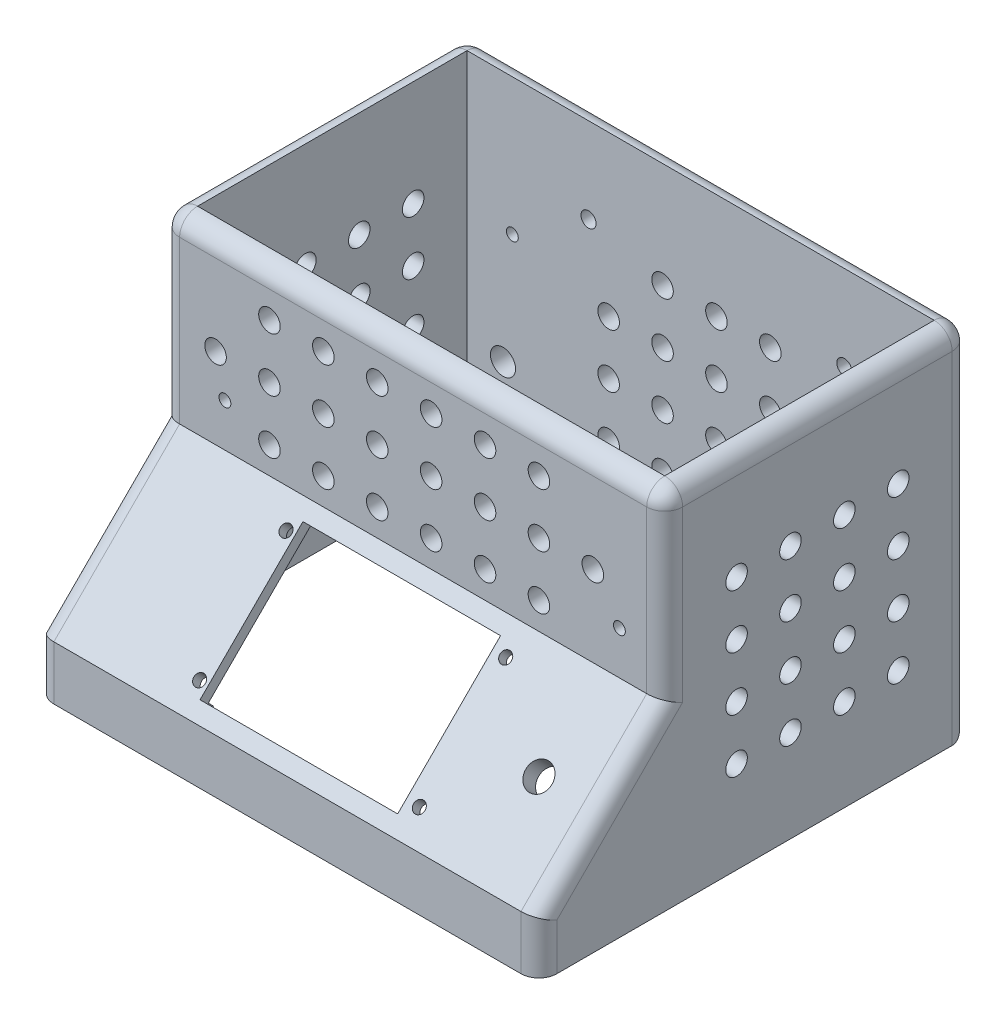
SolidWorks part; units mm, degrees
ref_plane "Alzado" through (0, 0, 0) normal (0, 0, 1) x (1, 0, 0)
ref_plane "Planta" through (0, 0, 0) normal (0, 1, 0) x (1, 0, 0)
ref_plane "Vista lateral" through (0, 0, 0) normal (1, 0, 0) x (0, 0, -1)
sketch "Sketch2" plane through (0, 0, 0) normal (1, 0, 0) x (0, 0, -1)
  line L0 (-77.5, -50) -> (-77.5, -35)
  line L1 (-42.5, 50) -> (42.5, 50)
  line L2 (-42.5, 50) -> (-42.5, -50)
  line L3 (-42.5, -50) -> (42.5, -50)
  line L4 (42.5, 50) -> (42.5, -50)
  line L5 (-42.5, 50) -> (42.5, -50) construction
  line L6 (-42.5, -50) -> (42.5, 50) construction
  line L7 (-77.5, -50) -> (-42.5, -50)
  line L8 (-77.5, -35) -> (-42.5, 0)
  line L9 (-77.5, -35) -> (-42.5, -35) construction
  point P0 (0, 0)
  dimension "D1" = 45
  dimension "D2" = 85
  dimension "D3" = 35
  dimension "D4" = 100
  dimension "D5" = 15
extrude "Boss-Extrude1" add sketch "Sketch2" along normal mid plane 140
shell "Shell1" thickness 5
sketch "Sketch3" plane through (0, -50, 0) normal (0, -1, 0) x (1, 0, 0)
  line L1 (-65, 72.5) -> (65, 72.5)
  line L2 (-65, 72.5) -> (-65, -37.5)
  line L3 (-65, -37.5) -> (65, -37.5)
  line L4 (-70, 77.5) -> (-70, -42.5)
  line L5 (-70, -42.5) -> (70, -42.5)
  line L6 (70, -42.5) -> (70, 77.5)
  line L7 (70, 77.5) -> (-70, 77.5)
  line L8 (-70, 77.5) -> (-70, -42.5)
  line L9 (-70, -42.5) -> (70, -42.5)
  line L10 (70, -42.5) -> (70, 77.5)
  line L11 (70, 77.5) -> (-70, 77.5)
  line L12 (65, 72.5) -> (65, -37.5)
  line L13 (-65, 72.5) -> (65, -37.5) construction
  line L14 (-65, -37.5) -> (65, 72.5) construction
  point P2 (0, 17.5)
  dimension "D2" = 5
  dimension "D3" = 5
  dimension "D4" = 5
  dimension "D5" = 5
  dimension "D1" = 0
extrude "Cut-Extrude1" cut sketch "Sketch3" against normal up to surface (5 mm away) contours L2 L1 L12 L3
sketch "Sketch4" plane through (0, 21.25, 21.25) normal (0, 0.7071, 0.7071) x (1, 0, 0)
  line L0 (70, -79.5495) -> (-70, -30.052) construction
  line L1 (-70, -79.5495) -> (70, -30.052) construction
  line L3 (-27.5, -34.5508) -> (27.5, -34.5508)
  line L4 (-70, -30.052) -> (-70, -79.5495)
  line L5 (-70, -79.5495) -> (70, -79.5495)
  line L6 (70, -79.5495) -> (70, -30.052)
  line L7 (70, -30.052) -> (-70, -30.052)
  line L8 (-70, -30.052) -> (-70, -79.5495)
  line L9 (-70, -79.5495) -> (70, -79.5495)
  line L10 (70, -79.5495) -> (70, -30.052)
  line L11 (70, -30.052) -> (-70, -30.052)
  line L12 (-27.5, -34.5508) -> (-27.5, -75.0508)
  line L13 (-27.5, -75.0508) -> (27.5, -75.0508)
  line L14 (27.5, -34.5508) -> (27.5, -75.0508)
  line L15 (-27.5, -34.5508) -> (27.5, -75.0508) construction
  line L16 (-27.5, -75.0508) -> (27.5, -34.5508) construction
  point P2 (0, -54.8008)
  dimension "D2" = 55
  dimension "D3" = 40.5
  dimension "D1" = 0
extrude "Cut-Extrude2" cut sketch "Sketch4" against normal up to surface (5 mm away) contours L12 L3 L14 L13 up to face at (0, -19.5711, 55)
sketch "Sketch5" plane through (0, 50, 0) normal (0, 1, 0) x (1, 0, 0)
  line L0 (65, -37.5) -> (65, 37.5) construction
  line L1 (54.7, -27.2) -> (65, -27.2)
  line L2 (54.7, -27.2) -> (54.7, -37.5)
  line L3 (54.7, -37.5) -> (65, -37.5)
  line L4 (-70, 42.5) -> (-70, -42.5)
  line L5 (-70, -42.5) -> (70, -42.5)
  line L6 (70, -42.5) -> (70, 42.5)
  line L7 (70, 42.5) -> (-70, 42.5)
  line L10 (70, -42.5) -> (70, 42.5)
  line L12 (65, -27.2) -> (65, -37.5)
  line L13 (54.7, -27.2) -> (65, -37.5) construction
  line L14 (54.7, -37.5) -> (65, -27.2) construction
  line L15 (65, -37.5) -> (-65, -37.5) construction
  line L17 (65, 37.5) -> (-65, 37.5) construction
  line L32 (-55.2, -27.2) -> (-55.2, -37.5)
  line L33 (-55.2, -27.2) -> (-44.9, -27.2)
  line L34 (-44.9, -27.2) -> (-44.9, -37.5)
  line L35 (-55.2, -37.5) -> (-44.9, -37.5)
  line L36 (-55.2, 37.5) -> (-55.2, 27.2)
  line L37 (-55.2, 37.5) -> (-44.9, 37.5)
  line L38 (-44.9, 37.5) -> (-44.9, 27.2)
  line L39 (-55.2, 27.2) -> (-44.9, 27.2)
  line L40 (54.7, 37.5) -> (54.7, 27.2)
  line L41 (54.7, 37.5) -> (65, 37.5)
  line L42 (65, 37.5) -> (65, 27.2)
  line L43 (54.7, 27.2) -> (65, 27.2)
  circle A0 centre (59.85, -32.35) radius 1.65
  circle A4 centre (-50.05, -32.35) radius 1.65
  circle A5 centre (-50.05, 32.35) radius 1.65
  circle A6 centre (59.85, 32.35) radius 1.65
  point P2 (59.85, -32.35)
  line M14 (65, -37.5) -> (-65, -37.5)
  line M16 (-65, 37.5) -> (65, 37.5)
  line M17 (65, 37.5) -> (65, -37.5)
  dimension "D2" = 3.3
  dimension "D7" = 106.6
  dimension "D8" = 0
  dimension "D9" = 64.7
  dimension "D3" = 3.5
  dimension "D4" = 3.5
  dimension "D5" = 2
  dimension "D1" = 0
  dimension "D6" = 2
extrude "Boss-Extrude2" add sketch "Sketch5" against normal blind 7 separate body contours L36 L39 L38 A5 M16 | L34 L33 L32 A4 M14 | L40 L43 A6 M17 M16 | L1 L2 A0 M14 M17
sketch "Sketch6" plane through (0, 21.25, 21.25) normal (0, 0.7071, 0.7071) x (1, 0, 0)
  line L0 (27.5, -34.5508) -> (27.5, -75.0508) construction
  line L4 (-70, -30.052) -> (-70, -79.5495)
  line L5 (-70, -79.5495) -> (70, -79.5495)
  line L6 (70, -79.5495) -> (70, -30.052)
  line L7 (70, -30.052) -> (-70, -30.052)
  line L8 (-70, -30.052) -> (-70, -79.5495)
  line L9 (-70, -79.5495) -> (70, -79.5495)
  line L10 (70, -79.5495) -> (70, -30.052)
  line L11 (70, -30.052) -> (-70, -30.052)
  circle A0 centre (52.5, -54.8008) radius 3.65
  point P9 (27.5, -54.8008)
  dimension "D2" = 7.3
  dimension "D3" = 25
  dimension "D1" = 0
extrude "Cut-Extrude3" cut sketch "Sketch6" against normal blind 10 contours A0
sketch "Sketch7" plane through (0, -50, 0) normal (0, -1, 0) x (1, 0, 0)
  line L16 (65, -37.5) -> (65, -27.2) construction
  line L17 (54.7, -37.5) -> (65, -37.5) construction
  line L18 (54.7, -37.5) -> (54.7, -27.2) construction
  line L28 (54.7, -27.2) -> (65, -27.2) construction
  line L29 (65, -37.5) -> (65, -27.2)
  line L30 (54.7, -37.5) -> (65, -37.5)
  line L31 (-70, 77.5) -> (-70, -42.5)
  line L32 (-70, -42.5) -> (70, -42.5)
  line L33 (70, -42.5) -> (70, 77.5)
  line L34 (70, 77.5) -> (-70, 77.5)
  line L35 (-70, 77.5) -> (-70, -42.5)
  line L36 (-70, -42.5) -> (70, -42.5)
  line L37 (70, -42.5) -> (70, 77.5)
  line L38 (70, 77.5) -> (-70, 77.5)
  line L39 (54.7, -37.5) -> (54.7, -27.2)
  line L40 (54.7, -27.2) -> (65, -27.2)
  line L41 (-54.7, -37.5) -> (-54.7, -27.2)
  line L42 (-65, -27.2) -> (-54.7, -27.2)
  line L43 (-65, -37.5) -> (-65, -27.2)
  line L44 (-65, -37.5) -> (-54.7, -37.5)
  line L45 (-54.7, 62.2) -> (-54.7, 72.5)
  line L46 (-65, 72.5) -> (-54.7, 72.5)
  line L47 (-65, 62.2) -> (-65, 72.5)
  line L48 (-65, 62.2) -> (-54.7, 62.2)
  line L49 (65, 62.2) -> (65, 72.5)
  line L50 (54.7, 72.5) -> (65, 72.5)
  line L51 (54.7, 62.2) -> (54.7, 72.5)
  line L52 (54.7, 62.2) -> (65, 62.2)
  line L53 (-65, 72.5) -> (-65, -37.5) construction
  line L54 (65, 72.5) -> (-65, 72.5) construction
  circle A7 centre (59.85, -32.35) radius 1.65 construction
  circle A8 centre (59.85, -32.35) radius 1.65
  circle A9 centre (-59.85, -32.35) radius 1.65
  circle A10 centre (-59.85, 67.35) radius 1.65
  circle A11 centre (59.85, 67.35) radius 1.65
  dimension "D3" = 2
  dimension "D1" = 2
  dimension "D2" = 0
extrude "Boss-Extrude3" add sketch "Sketch7" against normal blind 5
sketch "Sketch8" plane through (0, -45, 0) normal (0, 1, 0) x (1, 0, 0)
  line L0 (-61.5, 35.15) -> (-63.2464, 32.35)
  line L1 (-63.2464, 32.35) -> (-61.5, 29.55)
  line L2 (-61.5, 29.55) -> (-58.2, 29.55)
  line L3 (-56.4536, 32.35) -> (-58.2, 29.55)
  line L4 (-56.4536, 32.35) -> (-58.2, 35.15)
  line L5 (-61.5, 35.15) -> (-58.2, 35.15)
  line L6 (-61.5, -64.55) -> (-63.2464, -67.35)
  line L7 (-63.2464, -67.35) -> (-61.5, -70.15)
  line L8 (-61.5, -70.15) -> (-58.2, -70.15)
  line L9 (-56.4536, -67.35) -> (-58.2, -70.15)
  line L10 (-56.4536, -67.35) -> (-58.2, -64.55)
  line L11 (-61.5, -64.55) -> (-58.2, -64.55)
  line L12 (65, 27.2) -> (65, 37.5) construction
  line L13 (65, 37.5) -> (54.7, 37.5) construction
  line L14 (58.2, -64.55) -> (56.4536, -67.35)
  line L15 (56.4536, -67.35) -> (58.2, -70.15)
  line L28 (65, 27.2) -> (65, 37.5)
  line L29 (65, 37.5) -> (54.7, 37.5)
  line L32 (58.2, 29.55) -> (61.5, 29.55)
  line L39 (58.2, 35.15) -> (61.5, 35.15)
  line L42 (63.2464, 32.35) -> (61.5, 29.55)
  line L45 (56.4536, 32.35) -> (58.2, 29.55)
  line L70 (63.2464, 32.35) -> (61.5, 35.15)
  line L71 (58.2, 35.15) -> (56.4536, 32.35)
  line L88 (58.2, -70.15) -> (61.5, -70.15)
  line L89 (63.2464, -67.35) -> (61.5, -70.15)
  line L90 (63.2464, -67.35) -> (61.5, -64.55)
  line L91 (58.2, -64.55) -> (61.5, -64.55)
  circle A0 centre (-59.85, 32.35) radius 1.65 construction
  circle A6 centre (-59.85, 32.35) radius 1.65
  circle A10 centre (-59.85, -67.35) radius 1.65
  circle A11 centre (59.85, -67.35) radius 1.65
  circle A12 centre (59.85, 32.35) radius 1.65 construction
  circle A13 centre (59.85, 32.35) radius 1.65
  circle A15 centre (-59.85, -67.35) radius 1.65 construction
  point P15 (59.85, 29.55)
  point P33 (59.85, 35.15)
  dimension "D9" = 5.6
  dimension "D1" = 3.3
  dimension "D2" = 3.3
  dimension "D3" = 3.3
  dimension "D4" = 3.3
  dimension "D5" = 3.3
  dimension "D6" = 3.3
  dimension "D7" = 2
  dimension "D8" = 2
extrude "Cut-Extrude4" cut sketch "Sketch8" against normal blind 3
sketch "Sketch14" plane through (0, 0, -42.5) normal (0, 0, -1) x (-1, 0, 0)
  line L0 (70, 50) -> (70, -50) construction
  line L4 (70, -50) -> (70, 50)
  line L5 (70, 50) -> (-70, 50)
  line L6 (-70, 50) -> (-70, -50)
  line L7 (-70, -50) -> (70, -50)
  line L11 (-70, -50) -> (70, -50)
  circle A0 centre (55, -20) radius 3.5
  dimension "D2" = 7
  dimension "D3" = 15
  dimension "D4" = 30
  dimension "D1" = 0
extrude "Cut-Extrude19" cut sketch "Sketch14" against normal up to surface (5 mm away) contours A0 up to face at (0, -22.5, -37.5)
sketch "Sketch23" plane through (0, 0, -42.5) normal (0, 0, -1) x (-1, 0, 0)
  line L1 (-70, -50) -> (70, -50) construction
  line L2 (-70, 50) -> (-70, -50) construction
  circle A0 centre (-40, -45) radius 2.1
  circle A1 centre (-40, 26.2) radius 2.1
  circle A2 centre (31.2, -45) radius 2.1
  circle A3 centre (31.2, 26.2) radius 2.1
  dimension "D1" = 67
  dimension "D2" = 4.2
  dimension "D3" = 4.2
  dimension "D4" = 67
  dimension "D5" = 67
  dimension "D6" = 4.2
  dimension "D7" = 4.2
  dimension "D8" = 30
  dimension "D9" = 5
extrude "Cut-Extrude21" cut sketch "Sketch23" against normal up to surface (5 mm away) up to face at (-55, -16.5, -37.5)
sketch "Sketch22" plane through (0, 43, 0) normal (0, -1, 0) x (1, 0, 0)
  line L0 (-55.2, -27.2) -> (-55.2, -37.5) construction
  line L2 (-44.9, -37.5) -> (-44.9, -27.2) construction
  line L3 (-44.9, -27.2) -> (-55.2, -27.2) construction
  line L4 (54.7, -27.2) -> (54.7, -37.5)
  line L5 (54.7, -37.5) -> (65, -37.5)
  line L6 (65, -37.5) -> (65, -27.2)
  line L7 (65, -27.2) -> (54.7, -27.2)
  line L8 (54.7, -27.2) -> (54.7, -37.5)
  line L9 (54.7, -37.5) -> (65, -37.5)
  line L10 (65, -37.5) -> (65, -27.2)
  line L11 (65, -27.2) -> (54.7, -27.2)
  line L12 (-44.9, 27.2) -> (-44.9, 37.5) construction
  line L14 (-55.2, 37.5) -> (-55.2, 27.2) construction
  line L15 (-55.2, 27.2) -> (-44.9, 27.2) construction
  line L16 (54.7, 27.2) -> (65, 27.2) construction
  line L17 (65, 27.2) -> (65, 37.5) construction
  line L18 (65, 37.5) -> (54.7, 37.5) construction
  line L19 (54.7, 37.5) -> (54.7, 27.2) construction
  line L20 (-55.2, -27.2) -> (-55.2, -37.5)
  line L22 (-44.9, -37.5) -> (-44.9, -27.2)
  line L23 (-44.9, -27.2) -> (-55.2, -27.2)
  line L24 (-44.9, 27.2) -> (-44.9, 37.5)
  line L26 (-55.2, 37.5) -> (-55.2, 27.2)
  line L27 (-55.2, 27.2) -> (-44.9, 27.2)
  line L28 (54.7, 27.2) -> (65, 27.2)
  line L29 (65, 27.2) -> (65, 37.5)
  line L30 (65, 37.5) -> (54.7, 37.5)
  line L31 (54.7, 37.5) -> (54.7, 27.2)
  line L32 (58.2, -35.15) -> (61.5, -35.15)
  line L33 (58.2, -29.55) -> (61.5, -29.55)
  line L34 (63.2464, -32.35) -> (61.5, -35.15)
  line L35 (56.4536, -32.35) -> (58.2, -35.15)
  line L36 (63.2464, -32.35) -> (61.5, -29.55)
  line L37 (58.2, -29.55) -> (56.4536, -32.35)
  line L38 (-51.7, -35.15) -> (-48.4, -35.15)
  line L39 (-46.6536, -32.35) -> (-48.4, -35.15)
  line L40 (-46.6536, -32.35) -> (-48.4, -29.55)
  line L41 (-51.7, -29.55) -> (-48.4, -29.55)
  line L42 (-51.7, -29.55) -> (-53.4464, -32.35)
  line L43 (-53.4464, -32.35) -> (-51.7, -35.15)
  line L44 (-51.7, 29.55) -> (-48.4, 29.55)
  line L45 (-46.6536, 32.35) -> (-48.4, 29.55)
  line L46 (-46.6536, 32.35) -> (-48.4, 35.15)
  line L47 (-51.7, 35.15) -> (-48.4, 35.15)
  line L48 (-51.7, 35.15) -> (-53.4464, 32.35)
  line L49 (-53.4464, 32.35) -> (-51.7, 29.55)
  line L50 (58.2, 29.55) -> (61.5, 29.55)
  line L51 (63.2464, 32.35) -> (61.5, 29.55)
  line L52 (63.2464, 32.35) -> (61.5, 35.15)
  line L53 (58.2, 35.15) -> (61.5, 35.15)
  line L54 (58.2, 35.15) -> (56.4536, 32.35)
  line L55 (56.4536, 32.35) -> (58.2, 29.55)
  circle A0 centre (-50.05, 32.35) radius 1.65 construction
  circle A1 centre (-50.05, 32.35) radius 1.65
  circle A2 centre (59.85, -32.35) radius 1.65 construction
  circle A3 centre (59.85, -32.35) radius 1.65
  circle A4 centre (59.85, -32.35) radius 1.65
  circle A5 centre (-50.05, -32.35) radius 1.65
  circle A6 centre (-50.05, 32.35) radius 1.65
  circle A7 centre (59.85, 32.35) radius 1.65
  circle A8 centre (59.85, 32.35) radius 1.65 construction
  circle A9 centre (-50.05, -32.35) radius 1.65 construction
  point P19 (59.85, -35.15)
  point P30 (59.85, -29.55)
  circle M46 centre (-50.05, -32.35) radius 1.65
  dimension "D3" = 3.3
  dimension "D2" = 3.3
  dimension "D4" = 5.6
  dimension "D1" = 0
  dimension "D5" = 2
  dimension "D6" = 2
extrude "Cut-Extrude27" cut sketch "Sketch22" against normal blind 2 contours L48 L49 L44 L45 L46 L47 A1 | A1 | L54 L55 L50 L51 L52 L53 A7 | A7 | L33 L37 L35 L32 L34 L36 A3 | A3 | L42 L43 L38 L39 L40 L41 M46 | M46
sketch "Sketch20" plane through (0, 17.7145, 17.7145) normal (0, -0.7071, -0.7071) x (1, 0, 0)
  line L0 (34.25, 34.5508) -> (34.25, 74.8008)
  line L1 (27.5, 34.5508) -> (34.25, 34.5508)
  line L2 (34.25, 74.8008) -> (27.5, 74.8008)
  line L3 (-27.5, 74.8008) -> (-33, 74.8008)
  line L4 (-33, 74.8008) -> (-33, 34.5508)
  line L5 (-33, 34.5508) -> (-27.5, 34.5508)
  line L6 (-27.5, 34.5508) -> (-27.5, 74.8008)
  line L7 (27.5, 74.8008) -> (27.5, 34.5508)
  line L8 (27.5, 75.0508) -> (27.5, 34.5508) construction
  line L9 (-27.5, 75.0508) -> (-27.5, 34.5508) construction
  line L10 (27.5, 34.5508) -> (-27.5, 34.5508) construction
  circle A0 centre (31.2, 37.7508) radius 1.6
  circle A1 centre (31.2, 71.7508) radius 1.6
  circle A2 centre (-29.95, 37.7508) radius 1.6
  circle A3 centre (-29.95, 71.7508) radius 1.6
  dimension "D3" = 3.2
  dimension "D4" = 3.2
  dimension "D7" = 3.2
  dimension "D8" = 3.2
  dimension "D9" = 3.05
  dimension "D16" = 3.2
  dimension "D10" = 3.05
  dimension "D11" = 3.7
  dimension "D2" = 40.25
  dimension "D5" = 67.25
  dimension "D6" = 61.15
extrude "Cut-Extrude20" cut sketch "Sketch20" against normal blind 2
fillet "Fillet1" radius 5 13 edges at (70, -42.5, 77.5) (70, -17.5, 60) (70, 25, 42.5) (70, 50, 0) (70, 0, -42.5) (-70, 50, 0) (-70, 25, 42.5) (-70, -17.5, 60) (-70, -42.5, 77.5) (-70, 0, -42.5) (0, -50, -42.5) (0, 50, -42.5) (0, 50, 42.5)
sketch "Sketch28" plane through (-70, 0, 0) normal (-1, 0, 0) x (0, 0, 1)
  line L0 (72.5, -50) -> (-37.5, -50) construction
  line L1 (-37.5, 45) -> (-37.5, -50) construction
  circle A0 centre (-22.5, 20.6) radius 3
  circle A1 centre (-7.5, 20.6) radius 3
  circle A2 centre (7.5, 20.6) radius 3
  circle A3 centre (22.5, 20.6) radius 3
  circle A4 centre (-7.5, 5.6) radius 3
  circle A5 centre (7.5, 5.6) radius 3
  circle A6 centre (22.5, 5.6) radius 3
  circle A7 centre (-7.5, -9.4) radius 3
  circle A8 centre (7.5, -9.4) radius 3
  circle A9 centre (22.5, -9.4) radius 3
  circle A10 centre (-7.5, -24.4) radius 3
  circle A11 centre (7.5, -24.4) radius 3
  circle A12 centre (22.5, -24.4) radius 3
  circle A13 centre (-22.5, 5.6) radius 3
  circle A14 centre (-22.5, -9.4) radius 3
  circle A15 centre (-22.5, -24.4) radius 3
  dimension "D1" = 70.6
  dimension "D2" = 6
  dimension "D3" = 12
  dimension "D6" = 15
  dimension "D7" = 15
  dimension "D4" = 4
  dimension "D5" = 4
extrude "Cut-Extrude22" cut sketch "Sketch28" against normal up to surface (140 mm away) up to face at (70, -8.1904, 24.1667)
sketch "Sketch29" plane through (0, 0, 42.5) normal (0, 0, 1) x (1, 0, 0)
  line L0 (65, 45) -> (-65, 45) construction
  line L1 (-65, 45) -> (-65, 0) construction
  line L3 (65, 0) -> (-65, 0) construction
  circle A0 centre (-55, 37.5) radius 3 construction
  circle A1 centre (-40, 37.5) radius 3
  circle A2 centre (-25, 37.5) radius 3
  circle A3 centre (-10, 37.5) radius 3
  circle A4 centre (5, 37.5) radius 3
  circle A5 centre (20, 37.5) radius 3
  circle A6 centre (35, 37.5) radius 3
  circle A8 centre (-40, 22.5) radius 3
  circle A9 centre (-25, 22.5) radius 3
  circle A10 centre (-10, 22.5) radius 3
  circle A11 centre (5, 22.5) radius 3
  circle A12 centre (20, 22.5) radius 3
  circle A13 centre (35, 22.5) radius 3
  circle A14 centre (50, 22.5) radius 3
  circle A15 centre (-40, 7.5) radius 3
  circle A16 centre (-25, 7.5) radius 3
  circle A17 centre (-10, 7.5) radius 3
  circle A18 centre (5, 7.5) radius 3
  circle A19 centre (20, 7.5) radius 3
  circle A20 centre (35, 7.5) radius 3
  circle A22 centre (-55, 22.5) radius 3
  circle A24 centre (-55, 7.5) radius 3 [skipped]
  circle A25 centre (50, 7.5) radius 3 [skipped]
  circle A26 centre (50, 37.5) radius 3 [skipped]
  dimension "D1" = 6
  dimension "D2" = 7.5
  dimension "D3" = 10
  dimension "D6" = 7.5
  dimension "D7" = 15
  dimension "D4" = 8
  dimension "D5" = 3
extrude "Cut-Extrude23" cut sketch "Sketch29" against normal up to surface (5 mm away) up to face at (0, 23.9645, 37.5)
sketch "Sketch30" plane through (0, 17.7145, 17.7145) normal (0, -0.7071, -0.7071) x (1, 0, 0)
  circle A0 centre (-29.95, 71.7508) radius 1.6 construction
  circle A1 centre (-29.95, 37.7508) radius 1.6 construction
  circle A2 centre (31.2, 37.7508) radius 1.6 construction
  circle A3 centre (31.2, 71.7508) radius 1.6 construction
  circle A4 centre (-29.95, 71.7508) radius 1.6
  circle A5 centre (-29.95, 37.7508) radius 1.6
  circle A6 centre (31.2, 37.7508) radius 1.6
  circle A7 centre (31.2, 71.7508) radius 1.6
extrude "Cut-Extrude24" cut sketch "Sketch30" against normal up to surface (5 mm away) up to face at (52.5, -20.0809, 62.5809)
sketch "Sketch31" plane through (0, 0, -42.5) normal (0, 0, -1) x (-1, 0, 0)
  line L0 (-40, 26.2) -> (31.2, -45) construction
  line L1 (31.2, 26.2) -> (-40, -45) construction
  line L2 (54.7, -50) -> (-54.7, -50) construction
  circle A0 centre (-34.4, 20.6) radius 3 construction
  circle A1 centre (-34.4, -39.4) radius 3 construction
  circle A2 centre (-19.4, 20.6) radius 3
  circle A3 centre (-4.4, 20.6) radius 3
  circle A4 centre (10.6, 20.6) radius 3
  circle A5 centre (-19.4, 5.6) radius 3
  circle A6 centre (-4.4, 5.6) radius 3
  circle A7 centre (10.6, 5.6) radius 3
  circle A8 centre (-19.4, -9.4) radius 3
  circle A9 centre (-4.4, -9.4) radius 3
  circle A10 centre (10.6, -9.4) radius 3
  circle A11 centre (-19.4, -24.4) radius 3
  circle A12 centre (-4.4, -24.4) radius 3
  circle A13 centre (10.6, -24.4) radius 3
  circle A14 centre (-34.4, 5.6) radius 3
  circle A15 centre (-34.4, -9.4) radius 3
  circle A16 centre (-34.4, -24.4) radius 3
  circle A17 centre (-19.4, -39.4) radius 3
  circle A18 centre (-4.4, -39.4) radius 3
  circle A19 centre (10.6, -39.4) radius 3
  circle A20 centre (25.6, 20.6) radius 3 construction
  circle A21 centre (25.6, 5.6) radius 3
  circle A22 centre (25.6, -9.4) radius 3
  circle A23 centre (25.6, -24.4) radius 3
  circle A24 centre (25.6, -39.4) radius 3 construction
  dimension "D1" = 6
  dimension "D2" = 70.6
  dimension "D3" = 5
  dimension "D5" = 15
  dimension "D6" = 15
  dimension "D4" = 5
extrude "Cut-Extrude26" cut sketch "Sketch31" against normal up to surface (5 mm away) up to face at (40, 28.3, -37.5)
sketch "Sketch32" plane through (0, 50, 0) normal (0, 1, 0) x (1, 0, 0)
  line L0 (65, -27.2) -> (54.7, -27.2) construction
  line L1 (54.7, -27.2) -> (54.7, -37.5) construction
  line L4 (54.7, 37.5) -> (54.7, 27.2) construction
  line L5 (54.7, 27.2) -> (65, 27.2) construction
  line L8 (-55.2, 37.5) -> (-55.2, 27.2) construction
  line L9 (-55.2, 27.2) -> (-44.9, 27.2) construction
  line L10 (-44.9, 27.2) -> (-44.9, 37.5) construction
  line L12 (-44.9, -37.5) -> (-44.9, -27.2) construction
  line L13 (-44.9, -27.2) -> (-55.2, -27.2) construction
  line L14 (-55.2, -27.2) -> (-55.2, -37.5) construction
  line L16 (65, -27.2) -> (54.7, -27.2)
  line L17 (54.7, -27.2) -> (54.7, -37.5)
  line L20 (54.7, 37.5) -> (54.7, 27.2)
  line L21 (54.7, 27.2) -> (65, 27.2)
  line L24 (-55.2, 37.5) -> (-55.2, 27.2)
  line L25 (-55.2, 27.2) -> (-44.9, 27.2)
  line L26 (-44.9, 27.2) -> (-44.9, 37.5)
  line L28 (-44.9, -37.5) -> (-44.9, -27.2)
  line L29 (-44.9, -27.2) -> (-55.2, -27.2)
  line L30 (-55.2, -27.2) -> (-55.2, -37.5)
  line L33 (70, -37.5) -> (70, 37.5) construction
  line L34 (-70, 37.5) -> (-65, 37.5)
  line L35 (-65, 37.5) -> (-65, 42.5)
  line L36 (-65, -37.5) -> (-65, -42.5)
  line L37 (-65, -42.5) -> (65, -42.5)
  line L38 (65, -42.5) -> (65, -37.5)
  line L39 (65, -37.5) -> (-65, -37.5)
  line L41 (-65, -42.5) -> (65, -42.5)
  line L43 (54.7, -37.5) -> (-44.9, -37.5)
  line L44 (-70, -37.5) -> (-65, -37.5)
  line L45 (-65, -37.5) -> (-65, 37.5)
  line L46 (-65, 37.5) -> (-70, 37.5)
  line L47 (-70, 37.5) -> (-70, -37.5)
  line L48 (-70, -37.5) -> (-65, -37.5)
  line L51 (-70, 37.5) -> (-70, -37.5)
  line L52 (-65, 42.5) -> (-65, 37.5)
  line L53 (-65, 37.5) -> (65, 37.5)
  line L54 (65, 37.5) -> (65, 42.5)
  line L55 (65, 42.5) -> (-65, 42.5)
  line L57 (-65, 37.5) -> (-55.2, 37.5)
  line L59 (65, 42.5) -> (-65, 42.5)
  line L60 (65, -37.5) -> (70, -37.5)
  line L61 (70, -37.5) -> (70, 37.5)
  line L62 (70, 37.5) -> (65, 37.5)
  line L63 (65, 37.5) -> (65, -37.5)
  line L64 (-44.9, 37.5) -> (54.7, 37.5)
  line L65 (70, -37.5) -> (70, 37.5)
  line L66 (-65, 37.5) -> (-65, -37.5)
  line L67 (65, 27.2) -> (65, -27.2)
  line L68 (-55.2, -37.5) -> (-65, -37.5)
  line L69 (-44.9, -37.5) -> (-55.2, -37.5)
  line L70 (-65, -42.5) -> (-65, -37.5)
  line L71 (-65, -37.5) -> (-70, -37.5)
  line L72 (-67.5, 40) -> (67.5, 40)
  line L73 (-65, -37.5) -> (-70, -37.5)
  line L74 (65, 37.5) -> (65, -37.5) construction
  line L79 (70, -37.5) -> (70, 37.5)
  line L80 (65, 27.2) -> (65, -27.2)
  line L84 (-67.5, 40) -> (-67.5, -40)
  line L85 (-67.5, -40) -> (67.5, -40)
  line L86 (67.5, 40) -> (67.5, -40)
  line L87 (-67.5, 40) -> (67.5, -40) construction
  line L88 (-67.5, -40) -> (67.5, 40) construction
  line L89 (54.7, -37.5) -> (65, -37.5)
  line L90 (65, -37.5) -> (65, -27.2)
  line L91 (65, 27.2) -> (65, 37.5)
  line L92 (65, 37.5) -> (54.7, 37.5)
  line L93 (-44.9, 37.5) -> (-55.2, 37.5)
  arc A0 (65, -42.5) -> (70, -37.5) centre (65, -37.5) ccw construction
  arc A1 (-65, 42.5) -> (-70, 37.5) centre (-65, 37.5) ccw
  arc A2 (-65, 42.5) -> (-70, 37.5) centre (-65, 37.5) ccw
  arc A3 (-70, -37.5) -> (-65, -42.5) centre (-65, -37.5) ccw
  arc A4 (-70, -37.5) -> (-65, -42.5) centre (-65, -37.5) ccw
  arc A5 (70, 37.5) -> (65, 42.5) centre (65, 37.5) ccw construction
  arc A6 (-65, 42.5) -> (-70, 37.5) centre (-65, 37.5) ccw construction
  arc A7 (65, -42.5) -> (70, -37.5) centre (65, -37.5) ccw
  arc A8 (70, 37.5) -> (65, 42.5) centre (65, 37.5) ccw
  arc A9 (-65, 42.5) -> (-70, 37.5) centre (-65, 37.5) ccw
  point P14 (0, 0)
  dimension "D7" = 2.5
  dimension "D8" = 2.5
  dimension "D1" = 0
  dimension "D2" = 0
  dimension "D3" = 0
  dimension "D4" = 0
  dimension "D5" = 0
  dimension "D6" = 0
extrude "Cut-Extrude28" cut sketch "Sketch32" against normal blind 10 contours L26 L93 L24 L25 | L91 L92 L20 L21 | L89 L90 L16 L17
sketch "Sketch34" plane through (0, 0, -37.5) normal (0, 0, 1) x (1, 0, 0)
  line L0 (-70, 45) -> (-70, -50) construction
  line L1 (65, 50) -> (-65, 50) construction
  line L2 (70, 2.6) -> (70, 8.6) construction
  circle A0 centre (-52.4, 12) radius 1.65
  circle A1 centre (57.4, 12) radius 1.65
  point P10 (0, 0)
  dimension "D1" = 3.3
  dimension "D2" = 17.6
  dimension "D3" = 38
  dimension "D4" = 12.6
  dimension "D5" = 3.3
extrude "Cut-Extrude30" cut sketch "Sketch34" against normal up to surface and the other way up to surface up to face at (34.4, 8.6, -42.5) other way up to face at (8, 7.5, 42.5)
